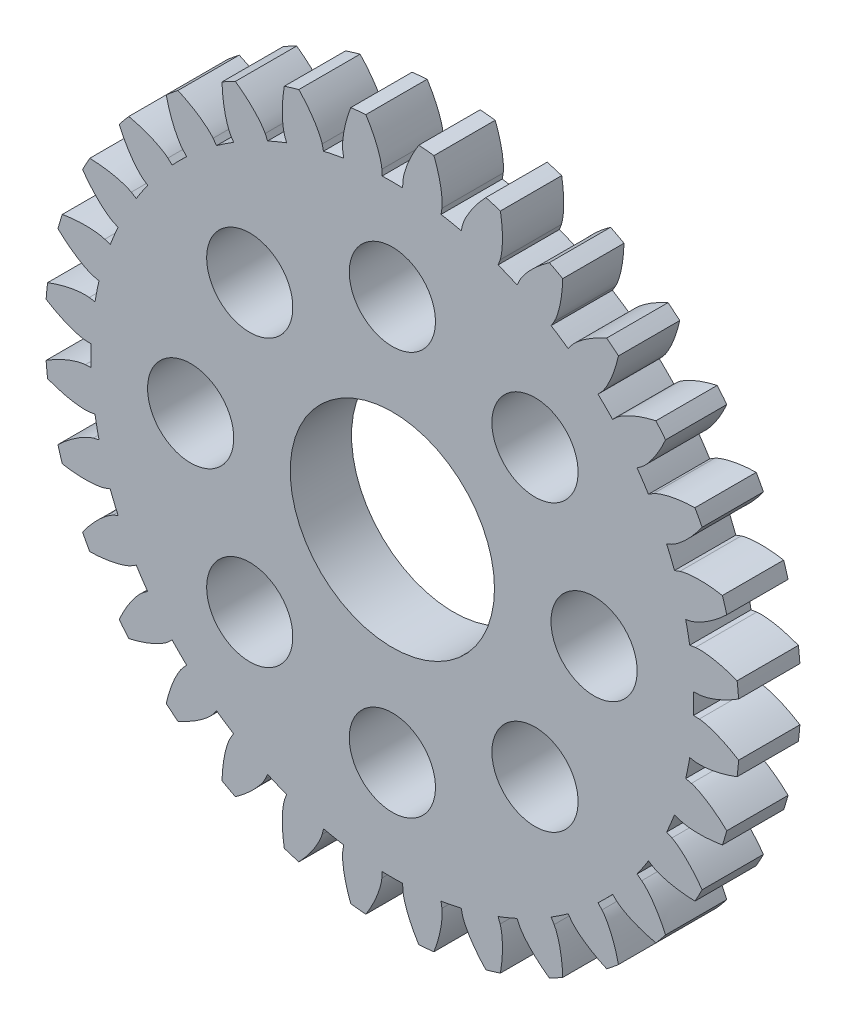
SolidWorks part; units mm, degrees
ref_plane "正面" through (0, 0, 0) normal (0, 0, 1) x (1, 0, 0)
ref_plane "平面" through (0, 0, 0) normal (0, 1, 0) x (1, 0, 0)
ref_plane "右側面" through (0, 0, 0) normal (1, 0, 0) x (0, 0, -1)
sketch "インボリュート スケッチ" plane through (0, 0, 0) normal (0, 0, 1) x (1, 0, 0)
  line L0 (-46.6927, -16.6405) -> (0.5138, -15.0263)
  line L1 (0.5138, -15.0263) -> (-0.5138, 15.0263) construction
  line L2 (0, 0) -> (0, 17) construction
  line L3 (-0.5138, 15.0263) -> (-0.5041, 14.7414)
  line L4 (0, 0) -> (0.5138, -15.0263)
  line L5 (-0.5041, 14.7414) -> (0, 14.7414)
  line L6 (0, 14.7414) -> (0, 0)
  circle A0 centre (0, 0) radius 15.0351 construction
  circle A1 centre (0, 0) radius 16 construction
  circle A2 centre (0, 0) radius 14.75 construction
  circle A3 centre (0, 0) radius 17 construction
  spline S0 degree 4 poles (-0.5138, 15.0263) (-0.5159, 15.0548) (-0.5218, 15.1117) (-0.5404, 15.2246) (-0.5892, 15.4367) (-0.6759, 15.716) (-0.8805, 16.2317) (-1.297, 17.0096) (-1.9931, 17.9739) (-3.1489, 19.1678) (-4.6974, 20.3489) (-6.5672, 21.3886) (-8.717, 22.22) (-10.9518, 22.779) (-13.2347, 23.082) (-15.65, 23.1478) (-18.6332, 22.9171) (-22.1316, 22.1876) (-26.0306, 20.7553) (-30.0637, 18.5141) (-33.7308, 15.7177) (-36.579, 12.8613) (-38.7428, 10.1707) (-40.3547, 7.7903) (-41.5274, 5.812) (-42.8455, 3.2575) (-43.965, 0.6074) (-44.8848, -2.1174) (-45.7495, -5.4571) (-46.2198, -8.0013) (-46.5006, -10.2863) (-46.6451, -12.2894) (-46.6919, -13.3002) (-46.7148, -14.1491) (-46.7213, -14.9318) (-46.7204, -15.5377) (-46.7026, -16.4013) (-46.6795, -17.0436) (-46.6261, -18.1011) (-46.5621, -18.9123) (-46.474, -19.9053) (-46.372, -20.7834) (-46.25, -21.7319) (-46.1122, -22.627) (-45.9948, -23.3298) (-45.9116, -23.7755) (-45.8682, -24.0076) knots 0 0 0 0 0 0.001401 0.002802 0.005604 0.010661 0.015718 0.02996 0.048734 0.068727 0.096889 0.125051 0.153212 0.181374 0.209535 0.237696 0.271429 0.327752 0.384075 0.440398 0.496721 0.553044 0.581206 0.609367 0.637529 0.66569 0.722013 0.750174 0.778336 0.834659 0.84874 0.86282 0.876901 0.883942 0.890982 0.900036 0.909091 0.920455 0.931818 0.943182 0.954545 0.965909 0.977273 0.988636 1 1 1 1 1 construction
  spline S1 degree 4 poles (-0.5138, 15.0263) (-0.5159, 15.0548) (-0.5218, 15.1117) (-0.5404, 15.2246) (-0.5892, 15.4367) (-0.6759, 15.716) (-0.8805, 16.2317) (-1.297, 17.0096) (-1.9931, 17.9739) (-3.1489, 19.1678) (-4.6974, 20.3489) (-6.5672, 21.3886) (-8.717, 22.22) (-10.9518, 22.779) (-13.2347, 23.082) (-15.65, 23.1478) (-18.6332, 22.9171) (-22.1316, 22.1876) (-26.0306, 20.7553) (-30.0637, 18.5141) (-33.7308, 15.7177) (-36.579, 12.8613) (-38.7428, 10.1707) (-40.3547, 7.7903) (-41.5274, 5.812) (-42.8455, 3.2575) (-43.965, 0.6074) (-44.8848, -2.1174) (-45.7495, -5.4571) (-46.2198, -8.0013) (-46.5006, -10.2863) (-46.6451, -12.2894) (-46.6919, -13.3002) (-46.7148, -14.1491) (-46.7213, -14.9318) (-46.7204, -15.5377) (-46.7081, -16.1325) (-46.6984, -16.4727) (-46.6927, -16.6405) knots 0 0 0 0 0 0.001401 0.002802 0.005604 0.010661 0.015718 0.02996 0.048734 0.068727 0.096889 0.125051 0.153212 0.181374 0.209535 0.237696 0.271429 0.327752 0.384075 0.440398 0.496721 0.553044 0.581206 0.609367 0.637529 0.66569 0.722013 0.750174 0.778336 0.834659 0.84874 0.86282 0.876901 0.883942 0.890982 0.900036 0.909091 0.909091 0.909091 0.909091 0.909091
  point P6 (-0.7851, 15.9807)
  point P12 (0, 16)
  point P24 (0, 0)
  dimension "D1" = 30.0702
  dimension "D2" = 32
  dimension "D3" = 29.5
  dimension "D4" = 34
  dimension "D5" = 0.7854
extrude "インボリュート ボス" add sketch "インボリュート スケッチ" along normal blind 3 contours S1 L0 L4 region at (-21.138, 1.3292, 0)
mirror "インボリュート ミラー" about plane through (0, 0, 3) normal (1, 0, 0) of bodies 161
sketch "歯先円 スケッチ" plane through (0, 0, 3) normal (0, 0, 1) x (1, 0, 0)
  circle A0 centre (0, 0) radius 49.5693
  circle A1 centre (0, 0) radius 17
  dimension "D1" = 34
extrude "歯先円 カット" cut sketch "歯先円 スケッチ" against normal through all
sketch "歯分割 スケッチ" plane through (0, 0, 3) normal (0, 0, 1) x (1, 0, 0)
  line L0 (-1.6663, 16.9181) -> (0, 0)
  line L1 (0, 0) -> (1.6663, 16.9181)
  line L2 (0, 0) -> (0, 16) construction
  arc A0 (-1.6663, 16.9181) -> (1.6663, 16.9181) centre (0, 0) ccw
  circle A2 centre (0, 0) radius 16 construction
  arc A3 (-1.2962, 16.9505) -> (-7.4154, -15.2974) centre (0, 0) ccw construction
  point P9 (-1.5683, 15.923)
  point P10 (1.5683, 15.923)
  dimension "D1" = 32
  dimension "D2" = 3.1416
extrude "歯分割 カット" cut sketch "歯分割 スケッチ" against normal through all
pattern_circular "歯分割 円形コピー" count 32 over 360 about axis through (0, 0, 0) along (0, 0, 1) of bodies 166
sketch "歯底円 スケッチ" plane through (0, 0, 3) normal (0, 0, 1) x (1, 0, 0)
  circle A0 centre (0, 0) radius 14.75
  dimension "D1" = 29.5
extrude "歯底円 ボス" add sketch "歯底円 スケッチ" against normal through all
sketch "軸 丸穴 スケッチ" plane through (0, 0, 3) normal (0, 0, 1) x (1, 0, 0)
  circle A0 centre (0, 0) radius 5
  dimension "D1" = 10
extrude "軸 丸穴 カット" cut sketch "軸 丸穴 スケッチ" against normal through all
sketch "軸 キー溝 スケッチ" plane through (0, 0, 3) normal (0, 0, 1) x (1, 0, 0)
  line L2 (-1.5, 3.7081) -> (-1.5, 5.4)
  line L3 (-1.5, 5.4) -> (1.5, 5.4)
  line L4 (1.5, 3.7081) -> (1.5, 5.4)
  arc A0 (-1.5, 3.7081) -> (1.5, 3.7081) centre (0, 0) ccw
  dimension "D1" = 8
  dimension "D2" = 3
  dimension "D3" = 5.4
extrude "軸 キー溝 カット" [suppressed] cut sketch "軸 キー溝 スケッチ" against normal through all
sketch "軸 Dカット スケッチ" plane through (0, 0, 3) normal (0, 0, 1) x (1, 0, 0)
  line L0 (-2.3958, 3) -> (2.3958, 3)
  arc A0 (-2.828, 2.8289) -> (2.828, 2.8289) centre (0, 0) ccw
  arc A1 (-2.3958, 3) -> (-2.828, 2.8289) centre (-2.6458, 3) ccw
  arc A2 (2.828, 2.8289) -> (2.3958, 3) centre (2.6458, 3) ccw
  dimension "D1" = 8
  dimension "D3" = 0.5
  dimension "D2" = 3
extrude "軸 Dカット カット" [suppressed] cut sketch "軸 Dカット スケッチ" against normal through all
sketch "軸 角穴 スケッチ" plane through (0, 0, 3) normal (0, 0, 1) x (1, 0, 0)
  line L0 (-5.1, 5.1) -> (5.1, 5.1)
  line L1 (-5, -5) -> (5, -5) construction
  line L2 (-5, -5) -> (-5, 5) construction
  line L3 (-5, 5) -> (5, 5) construction
  line L4 (5, -5) -> (5, 5) construction
  line L5 (-5, -5) -> (5, 5) construction
  line L6 (-5, 5) -> (5, -5) construction
  line L7 (5.1, -5.1) -> (5.1, 5.1)
  line L8 (-5.1, -5.1) -> (5.1, -5.1)
  line L9 (-5.1, -5.1) -> (-5.1, 5.1)
  point P0 (0, 0)
  dimension "D1" = 10
  dimension "D2" = 0.1
extrude "軸 角穴 カット" [suppressed] cut sketch "軸 角穴 スケッチ" against normal through all
sketch "フランジ穴 スケッチ" plane through (0, 0, 3) normal (0, 0, 1) x (1, 0, 0)
  circle A0 centre (0, 12) radius 1.6
  circle A1 centre (12, 0) radius 1.6
  circle A2 centre (0, -12) radius 1.6
  circle A3 centre (-12, 0) radius 1.6
  point P12 (0, 0)
  dimension "D2" = 3.2
  dimension "D3" = 12
  dimension "D1" = 4
extrude "フランジ穴 カット" [suppressed] cut sketch "フランジ穴 スケッチ" against normal through all
sketch "合致用スケッチ" plane through (0, 0, 3) normal (0, 0, 1) x (1, 0, 0)
  line L0 (0, 0) -> (0, 16)
  line L1 (0, 0) -> (1.5683, 15.923)
  circle A2 centre (0, 0) radius 16
  dimension "D1" = 32
  dimension "D2" = 5.625
sketch "ｽｹｯﾁ2" plane through (0, 0, 0) normal (0, 0, -1) x (-1, 0, 0)
  line L0 (0, -5) -> (0, -14.75) construction
  line L1 (-3.5355, -3.5355) -> (-10.4298, -10.4298) construction
  line L2 (-5, 0) -> (-14.75, 0) construction
  line L3 (-3.5355, 3.5355) -> (-10.4298, 10.4298) construction
  line L4 (0, 5) -> (0, 14.75) construction
  line L5 (3.5355, 3.5355) -> (10.4298, 10.4298) construction
  line L6 (5, 0) -> (14.75, 0) construction
  line L7 (3.5355, -3.5355) -> (10.4298, -10.4298) construction
  circle A0 centre (0, 0) radius 5 construction
  arc A1 (-0.5041, -14.7414) -> (0.5041, -14.7414) centre (0, 0) ccw construction
  circle A2 centre (0, -9.875) radius 2.1098
  circle A3 centre (-6.9827, -6.9827) radius 2.1098
  circle A4 centre (-9.875, 0) radius 2.1098
  circle A5 centre (-6.9827, 6.9827) radius 2.1098
  circle A6 centre (0, 9.875) radius 2.1098
  circle A7 centre (6.9827, 6.9827) radius 2.1098
  circle A8 centre (9.875, 0) radius 2.1098
  circle A9 centre (6.9827, -6.9827) radius 2.1098
  point P9 (-6.5769, -0.6608)
  point P10 (0, 0)
  point P40 (0, 0)
  dimension "D1" = 4.2195
  dimension "D2" = 8
extrude "ｶｯﾄ - 押し出し1" cut sketch "ｽｹｯﾁ2" against normal through all
equation "\"モジュール\"= 1"
equation "\"基準圧力角\"= 20"
equation "\"歯数\"= 32"
equation "\"基準円直径\"= \"歯数\" * \"モジュール\""
equation "\"基礎円直径\"= \"基準円直径\" * cos ( \"基準圧力角\" )"
equation "\"歯先円直径\"= \"基準円直径\" + 2 * \"モジュール\""
equation "\"歯底円直径\"= \"基準円直径\" - 2.5 * \"モジュール\""
equation "\"D1@インボリュート スケッチ\" = \"基礎円直径\""
equation "\"D2@インボリュート スケッチ\" = \"基準円直径\""
equation "\"D3@インボリュート スケッチ\" = \"歯底円直径\""
equation "\"D4@インボリュート スケッチ\" = \"歯先円直径\""
equation "\"D5@インボリュート スケッチ\" = Pi * \"モジュール\" / 4"
equation "\"D1@歯先円 スケッチ\" = \"歯先円直径\""
equation "\"D1@歯分割 スケッチ\" = \"基準円直径\""
equation "\"D2@歯分割 スケッチ\" = PI * \"モジュール\""
equation "\"D1@歯分割 円形コピー\" = \"歯数\""
equation "\"D1@歯底円 スケッチ\" = \"歯底円直径\""
equation "\"板厚\"= 3"
equation "\"D1@インボリュート ボス\"=\"板厚\""
equation "\"D1@合致用スケッチ\" = \"基準円直径\""
equation "\"D2@合致用スケッチ\"=180/\"歯数\""
